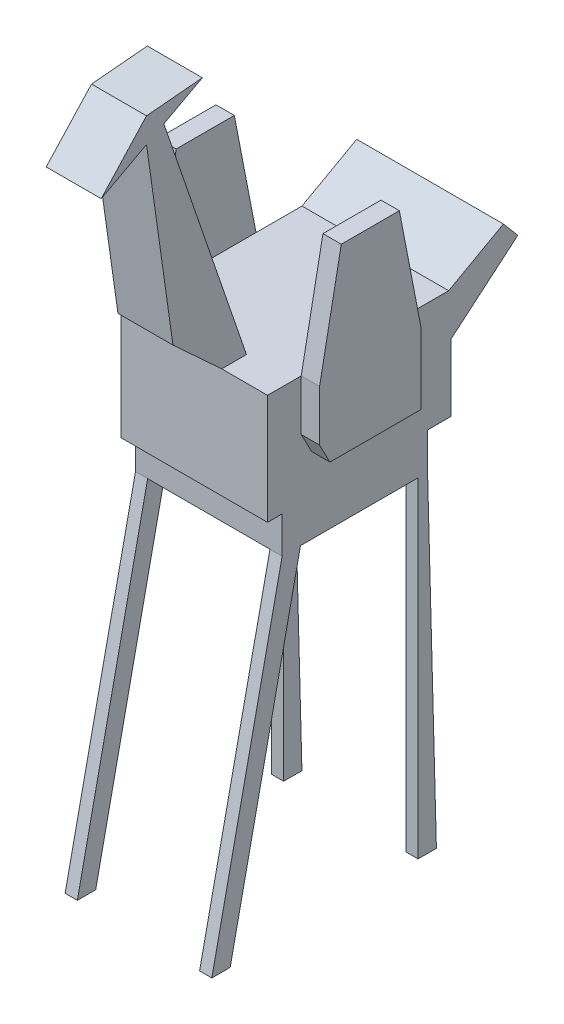
SolidWorks part; units mm, degrees
ref_plane "Front Plane" through (0, 0, 0) normal (0, 0, 1) x (1, 0, 0)
ref_plane "Top Plane" through (0, 0, 0) normal (0, 1, 0) x (1, 0, 0)
ref_plane "Right Plane" through (0, 0, 0) normal (1, 0, 0) x (0, 0, -1)
ref_axis "Axis1" through (0, 3399.178, 0) along (0, -1, 0)
ref_plane "Plane1" through (0, 0, 0) normal (0.9659, 0, 0.2588) x (0.2588, 0, -0.9659)
ref_axis "Axis2" through (-219.6132, 0, 819.6076) along (0.2588, 0, -0.9659)
ref_plane "Plane2" through (0, 0, 0) normal (0.933, -0.2588, 0.25) x (0.2588, 0, -0.9659)
sketch "Sketch1"
sketch "Sketch2" plane through (0, 0, 0) normal (1, 0, 0) x (0, 0, -1)
  line L0 (-73.4299, 2743.2) -> (0, 0)
  line L1 (-73.4299, 2743.2) -> (-1281.9052, 2743.2)
  line L2 (-1281.9052, 2743.2) -> (-1866.3884, 0)
  line L3 (-1866.3884, 0) -> (0, 0)
  line L4 (-819.6076, 0) -> (332.1152, 0) construction
  line L5 (-73.4299, 2743.2) -> (-73.4299, 3048)
  line L6 (-1403.3991, 3048) -> (120.6009, 3048)
  line L7 (-1281.9052, 2743.2) -> (-1281.9052, 3048)
  line L8 (120.6009, 3048) -> (120.6009, 3604.2334)
  line L9 (120.6009, 3604.2334) -> (676.482, 4073.8849)
  line L10 (676.482, 4073.8849) -> (556.9528, 4215.3601)
  line L11 (556.9528, 4215.3601) -> (102.0428, 3962.4)
  line L12 (102.0428, 3962.4) -> (-1403.3991, 3962.4)
  line L13 (-1403.3991, 3962.4) -> (-1403.3991, 3048)
  line L14 (-1403.3991, 3962.4) -> (-1808.3995, 4335.6764)
  line L15 (-1808.3995, 4335.6764) -> (-2028.3027, 5889.225)
  line L16 (-2028.3027, 5889.225) -> (-2404.6959, 5687.618)
  line L17 (-2404.6959, 5687.618) -> (-2028.3027, 6096)
  line L18 (-2028.3027, 6096) -> (-1564.127, 6137.8508)
  line L19 (-1564.127, 6137.8508) -> (-1884.2747, 5966.3705)
  line L20 (-1884.2747, 5966.3705) -> (-1197.533, 3962.4)
  line L21 (-1123.4246, 3962.4) -> (-1123.4246, 3540.6298)
  line L22 (-1123.4246, 3540.6298) -> (-1037.1014, 3374.7862)
  line L23 (-1037.1014, 3374.7862) -> (-279.8111, 3374.7862)
  line L24 (-279.8111, 3374.7862) -> (-279.8111, 3962.4)
  line L25 (-279.8111, 3962.4) -> (-460.3052, 4895.8974)
  line L26 (-460.3052, 4895.8974) -> (-942.9305, 4895.8974)
  line L27 (-942.9305, 4895.8974) -> (-1123.4246, 3962.4)
  line L28 (-701.6179, 4895.8974) -> (-701.6179, 3962.4) construction
  dimension "D1" = 1524
  dimension "D2" = 3048
  dimension "D3" = 304.8
  dimension "D4" = 914.4
  dimension "D5" = 2133.6
sketch "Sketch3" plane through (0, 0, 0) normal (1, 0, 0) x (0, 0, -1)
  line L0 (-1403.3991, 3962.4) -> (-1403.3991, 3048)
  line L1 (-1403.3991, 3048) -> (-1281.9052, 3048)
  line L2 (-1281.9052, 3048) -> (-1281.9052, 2743.2)
  line L3 (-1281.9052, 2743.2) -> (-73.4299, 2743.2)
  line L4 (-73.4299, 2743.2) -> (-73.4299, 3048)
  line L5 (-73.4299, 3048) -> (120.6009, 3048)
  line L6 (120.6009, 3048) -> (120.6009, 3604.2334)
  line L7 (120.6009, 3604.2334) -> (676.482, 4073.8849)
  line L8 (676.482, 4073.8849) -> (556.9528, 4215.3601)
  line L9 (556.9528, 4215.3601) -> (102.0428, 3962.4)
  line L10 (102.0428, 3962.4) -> (-1403.3991, 3962.4)
extrude "Boss-Extrude1" add sketch "Sketch3" along normal mid plane 1219.2
sketch "Sketch4" plane through (0, 0, 0) normal (1, 0, 0) x (0, 0, -1)
  line L0 (-1197.533, 3962.4) -> (-1884.2747, 5966.3705)
  line L1 (-1884.2747, 5966.3705) -> (-1564.127, 6137.8508)
  line L2 (-1564.127, 6137.8508) -> (-2028.3027, 6096)
  line L3 (-2028.3027, 6096) -> (-2404.6959, 5687.618)
  line L4 (-2404.6959, 5687.618) -> (-2028.3027, 5889.225)
  line L5 (-2028.3027, 5889.225) -> (-1808.3995, 4335.6764)
  line L6 (-1808.3995, 4335.6764) -> (-1403.3991, 3962.4)
  line L7 (-1403.3991, 3962.4) -> (-1197.533, 3962.4)
extrude "Boss-Extrude2" add sketch "Sketch4" along normal mid plane 457.2
sketch "Sketch5" plane through (609.6, 0, 0) normal (1, 0, 0) x (0, 0, -1)
  line L0 (-1281.9052, 2743.2) -> (-1866.3884, 0)
  line L1 (-1866.3884, 0) -> (-1713.9884, 0)
  line L2 (-1866.3884, 0) -> (0, 0) construction
  line L3 (-1713.9884, 0) -> (-1129.5052, 2743.2)
  line L4 (-73.4299, 2743.2) -> (-1281.9052, 2743.2) construction
  line L5 (-1129.5052, 2743.2) -> (-1281.9052, 2743.2)
  line L6 (-73.4299, 2743.2) -> (0, 0)
  line L7 (0, 0) -> (-152.4, 0)
  line L8 (-152.4, 0) -> (-152.4, 2743.2)
  line L9 (-152.4, 2743.2) -> (-73.4299, 2743.2)
  dimension "D1" = 152.4
extrude "Boss-Extrude3" add sketch "Sketch5" against normal blind 101.6
mirror "Mirror1" about plane through (0, 0, 0) normal (1, 0, 0) of "Boss-Extrude3"
sketch "Sketch6" plane through (609.6, 0, 0) normal (1, 0, 0) x (0, 0, -1)
  line L0 (-942.9305, 4895.8974) -> (-1123.4246, 3962.4)
  line L1 (-1123.4246, 3962.4) -> (-1123.4246, 3540.6298)
  line L2 (-1123.4246, 3540.6298) -> (-1037.1014, 3374.7862)
  line L3 (-1037.1014, 3374.7862) -> (-279.8111, 3374.7862)
  line L4 (-279.8111, 3374.7862) -> (-279.8111, 3962.4)
  line L5 (-279.8111, 3962.4) -> (-460.3052, 4895.8974)
  line L6 (-460.3052, 4895.8974) -> (-942.9305, 4895.8974)
extrude "Boss-Extrude4" add sketch "Sketch6" along normal blind 152.4
mirror "Mirror2" about plane through (0, 0, 0) normal (1, 0, 0) of "Boss-Extrude4"
